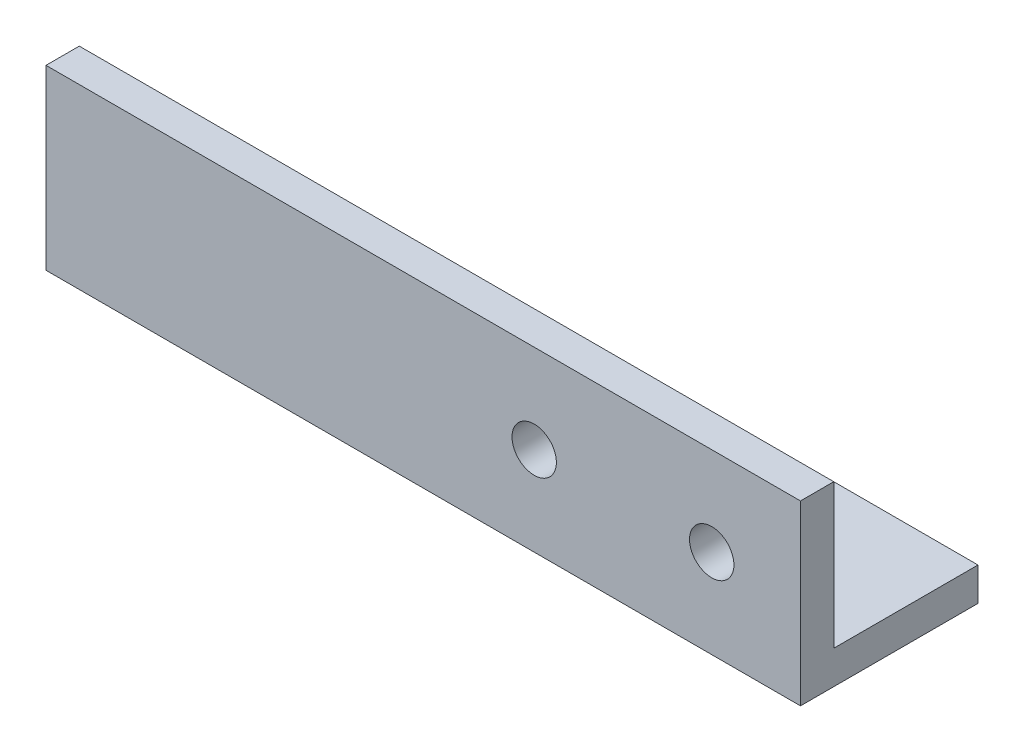
SolidWorks part; units mm, degrees
material "6061 Alloy"
ref_plane "Front Plane" through (0, 0, 0) normal (0, 0, 1) x (1, 0, 0)
ref_plane "Top Plane" through (0, 0, 0) normal (0, 1, 0) x (1, 0, 0)
ref_plane "Right Plane" through (0, 0, 0) normal (1, 0, 0) x (0, 0, -1)
sketch "Sketch1" plane through (0, 0, 0) normal (1, 0, 0) x (0, 0, -1)
  line L0 (0, 0) -> (0, -25.4)
  line L1 (0, -25.4) -> (25.4, -25.4)
  line L2 (25.4, -25.4) -> (25.4, -20.6375)
  line L3 (25.4, -20.6375) -> (4.7625, -20.6375)
  line L4 (4.7625, -20.6375) -> (4.7625, 0)
  line L5 (4.7625, 0) -> (0, 0)
  dimension "D1" = 4.7625
  dimension "D2" = 4.7625
  dimension "D3" = 25.4
  dimension "D4" = 25.4
extrude "Boss-Extrude1" add sketch "Sketch1" along normal blind 107.95
sketch "Sketch2" plane through (0, -20.6375, 0) normal (0, 1, 0) x (1, 0, 0)
  line L1 (0, 25.4) -> (0, 4.7625) construction
  line L2 (107.95, 0) -> (0, 0) construction
  circle A0 centre (9.525, 11.1125) radius 3.175
  circle A1 centre (19.05, 17.4625) radius 3.175
  dimension "D1" = 11.1125
  dimension "D2" = 17.4625
  dimension "D3" = 19.05
  dimension "D4" = 6.35
  dimension "D5" = 6.35
  dimension "D6" = 9.525
extrude "Cut-Extrude1" cut sketch "Sketch2" against normal up to next
sketch "Sketch3" plane through (0, -25.4, 0) normal (0, -1, 0) x (1, 0, 0)
  circle A0 centre (76.3322, -13.4704) radius 3.175 construction
  circle A1 centre (76.3322, -13.4704) radius 3.175
extrude "Cut-Extrude2" cut sketch "Sketch3" against normal up to next
sketch "Sketch6" plane through (0, 0, 0) normal (0, 0, 1) x (1, 0, 0)
  circle A0 centre (69.85, -12.7) radius 3.175 construction
  circle A1 centre (95.25, -12.7) radius 3.175 construction
  circle A2 centre (69.85, -12.7) radius 3.175
  circle A3 centre (95.25, -12.7) radius 3.175
extrude "Cut-Extrude3" cut sketch "Sketch6" against normal up to next
